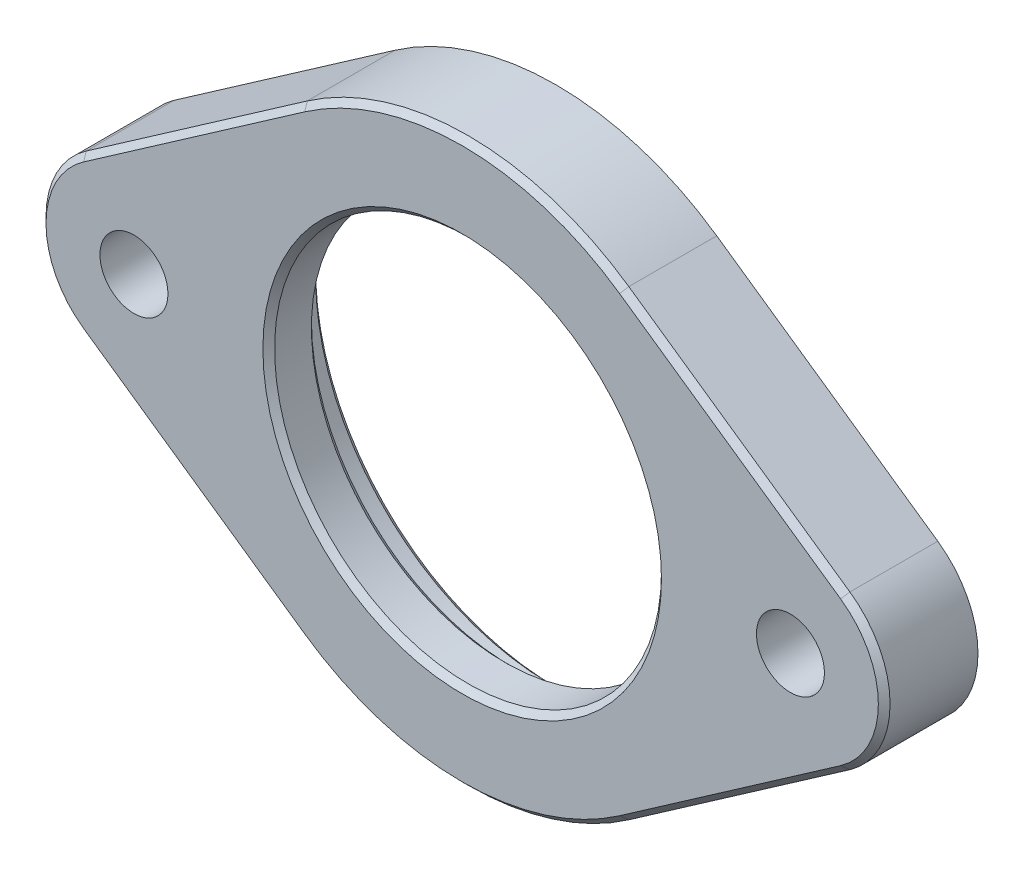
SolidWorks part; units mm, degrees
material "ABS"
ref_plane "Front Plane" through (0, 0, 0) normal (0, 0, 1) x (1, 0, 0)
ref_plane "Top Plane" through (0, 0, 0) normal (0, 1, 0) x (1, 0, 0)
ref_plane "Right Plane" through (0, 0, 0) normal (1, 0, 0) x (0, 0, -1)
sketch "Sketch1" plane through (0, 0, 0) normal (0, 0, 1) x (1, 0, 0)
  line L0 (-14, 0) -> (14, 0)
  line L1 (-6.8571, -9.8478) -> (-16.2857, -3.2826)
  line L2 (-6.8571, 9.8478) -> (-16.2857, 3.2826)
  line L3 (6.8571, 9.8478) -> (16.2857, 3.2826)
  line L4 (6.8571, -9.8478) -> (16.2857, -3.2826)
  circle A0 centre (0, 0) radius 8.25
  circle A1 centre (0, 0) radius 10
  circle A2 centre (0, 0) radius 12
  circle A3 centre (-14, 0) radius 4
  circle A4 centre (14, 0) radius 4
  point P7 (0, 0)
  dimension "D1" = 16.5
  dimension "D2" = 20
  dimension "D3" = 2
  dimension "D4" = 8
  dimension "D5" = 28
extrude "Boss-Extrude1" add sketch "Sketch1" along normal blind 4 contours A3 L0 A2 L2 | A3 L1 A2 L0 | A3 | A4 L3 A2 L0 | A4 | A4 L0 A2 L4 | A2 region at (14.6154, 0, 0) region at (11.8356, 5.4155, 0) region at (11.8356, -5.4155, 0) region at (-14.6154, 0, 0) region at (-11.8356, 5.4155, 0) region at (-11.8356, -5.4155, 0)
extrude "Cut-Extrude1" cut sketch "Sketch1<4>" against normal through all both and the other way through all contours L0 A0 | L0 A0 region at (0, -3.5014, 0) region at (0, 3.5014, 0)
sketch "Sketch1<4>" plane through (0, 0, 0) normal (0, 0, 1) x (1, 0, 0) same geometry as "Sketch1"
extrude "Cut-Extrude2" cut sketch "Sketch1<6>" along normal blind 1.93 and the other way through all contours A1
sketch "Sketch1<6>" plane through (0, 0, 0) normal (0, 0, 1) x (1, 0, 0) same geometry as "Sketch1"
sketch "Sketch2" plane through (0, 0, 4) normal (0, 0, 1) x (1, 0, 0)
  point P0 (-14, 0)
  point P3 (14, 0)
hole_wizard "M2.5 Clearance Hole1" positions "Sketch2" profile "Sketch3" hole size "M2.5" standard "ANSI Metric" end condition through all
sketch "Sketch3" plane through (-14, 0, 4) normal (1, 0, 0) x (0, -1, 0)
  line L0 (0, 0) -> (0, 4)
  line L1 (0, 4) -> (1.45, 4)
  line L2 (1.45, 4) -> (1.45, 0)
  line L5 (1.45, 0) -> (0, 0)
  line L11 (0, -6.35) -> (0, 107.95) construction
  dimension "Thru Hole Dia." = 2.9
  dimension "Thru Hole Depth" = 4
chamfer "Chamfer1" distance 0.25 angle 45 12 edges at (8.25, 0, 4) (8.25, 0, 1.93) (10, 0, 0) (10, 0, 1.93) (0, -12, 4) (11.5714, -6.5652, 4) (-11.5714, -6.5652, 4) (18, 0, 4) (-18, 0, 4) (11.5714, 6.5652, 4) (-11.5714, 6.5652, 4) (0, 12, 4)
